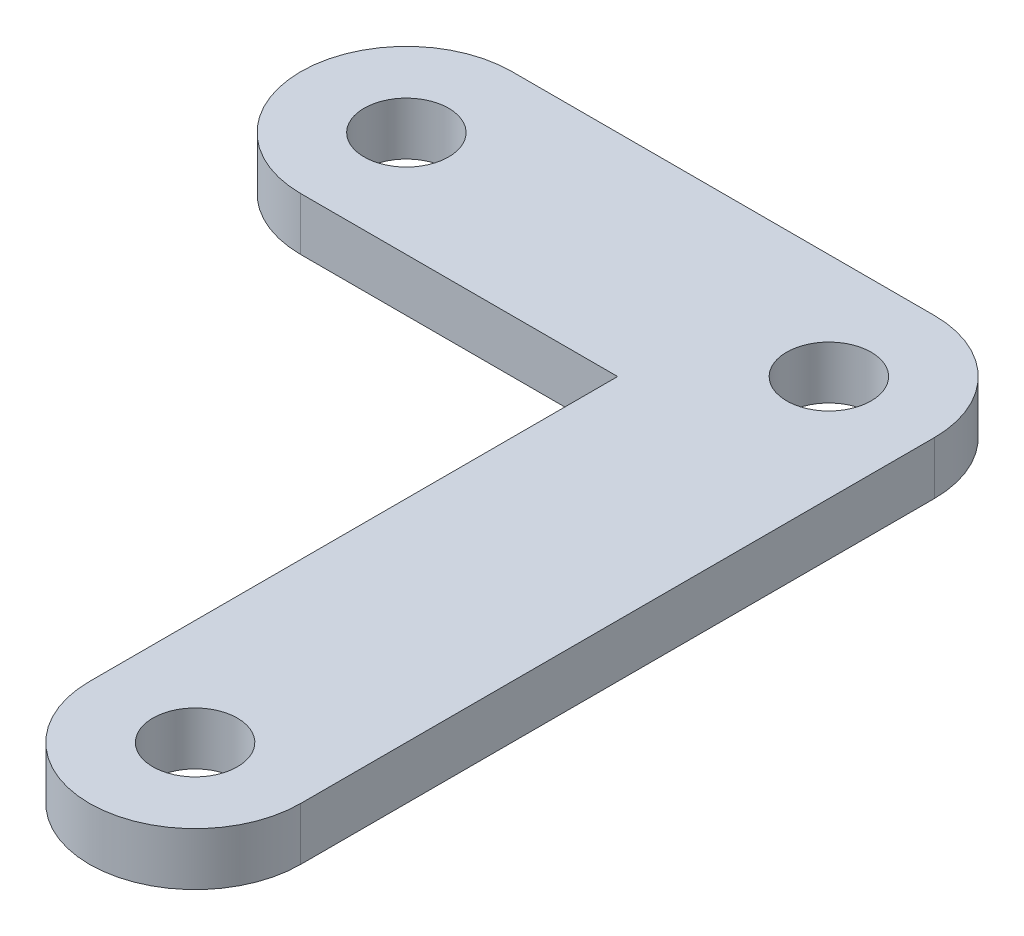
SolidWorks part; units mm, degrees
ref_plane "Front Plane" through (0, 0, 0) normal (0, 0, 1) x (1, 0, 0)
ref_plane "Top Plane" through (0, 0, 0) normal (0, 1, 0) x (1, 0, 0)
ref_plane "Right Plane" through (0, 0, 0) normal (1, 0, 0) x (0, 0, -1)
ref_axis "X" through (-88.99, 0, 0) along (1, 0, 0)
ref_axis "Y" through (0, 55, 0) along (0, -1, 0)
ref_axis "Z" through (0, 0, -88.99) along (0, 0, 1)
sketch "Sketch1" plane through (0, 0, 0) normal (0, 1, 0) x (1, 0, 0)
  line L0 (0, 0) -> (0, 60) construction
  line L1 (0, 60) -> (-40, 60) construction
  line L2 (-40, 70) -> (0, 70)
  line L3 (-40, 50) -> (-10, 50)
  line L4 (-10, 0) -> (-10, 50)
  line L5 (10, 60) -> (10, 0)
  circle A0 centre (0, 0) radius 10 construction
  circle A1 centre (0, 60) radius 10 construction
  circle A2 centre (-40, 60) radius 10 construction
  arc A3 (-40, 70) -> (-40, 50) centre (-40, 60) ccw
  arc A4 (0, 70) -> (10, 60) centre (0, 60) cw
  arc A5 (-10, 0) -> (10, 0) centre (0, 0) ccw
  dimension "D1" = 20
  dimension "D2" = 60
  dimension "D4" = 20
  dimension "D5" = 20
  dimension "D3" = 40
extrude "Boss-Extrude1" add sketch "Sketch1" along normal blind 5
sketch "Sketch2" plane through (0, 0, 0) normal (0, -1, 0) x (1, 0, 0)
  line L0 (-40, -60) -> (0, -60) construction
  line L1 (0, -60) -> (0, 0) construction
  circle A0 centre (0, 0) radius 4
  circle A1 centre (-40, -60) radius 4
  circle A2 centre (0, -60) radius 4
  dimension "D1" = 8
  dimension "D2" = 8
  dimension "D3" = 8
extrude "Cut-Extrude1" cut sketch "Sketch2" against normal blind 5
